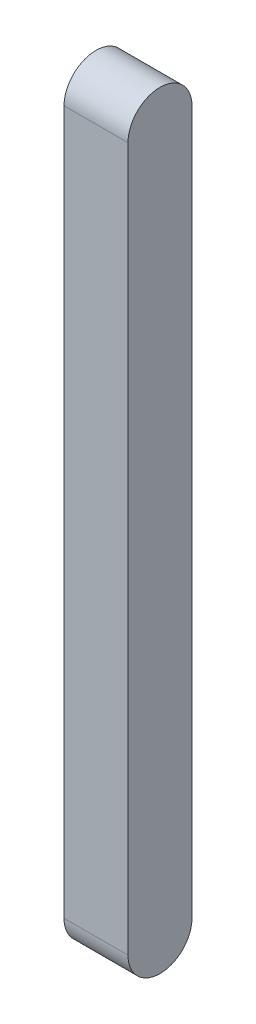
SolidWorks part; units mm, degrees
material "ABS"
ref_plane "前视基准面" through (0, 0, 0) normal (0, 0, 1) x (1, 0, 0)
ref_plane "上视基准面" through (0, 0, 0) normal (0, 1, 0) x (1, 0, 0)
ref_plane "右视基准面" through (0, 0, 0) normal (1, 0, 0) x (0, 0, -1)
sketch "草图1" plane through (0, 0, 0) normal (1, 0, 0) x (0, 0, -1)
  line L1 (-5, 55) -> (5, 55)
  line L2 (-5, 55) -> (-5, -55)
  line L3 (-5, -55) -> (5, -55)
  line L4 (5, 55) -> (5, -55)
  line L5 (-5, 55) -> (5, -55) construction
  line L6 (-5, -55) -> (5, 55) construction
  circle A0 centre (0, 55) radius 5
  circle A1 centre (0, -55) radius 5
  point P0 (0, 0)
extrude "凸台-拉伸1" add sketch "草图1" along normal blind 10 contours A0 | L2 L3 L4 L1 | A1
